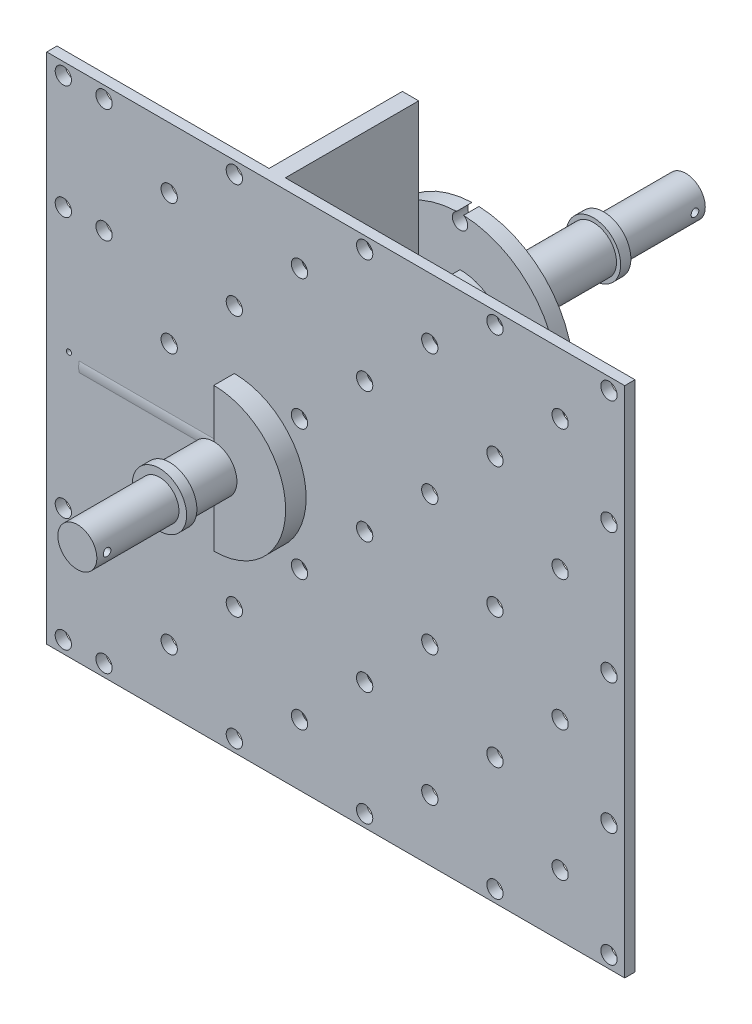
SolidWorks part; units mm, degrees
ref_plane "Front Plane" through (0, 0, 0) normal (0, 0, 1) x (1, 0, 0)
ref_plane "Top Plane" through (0, 0, 0) normal (0, 1, 0) x (1, 0, 0)
ref_plane "Right Plane" through (0, 0, 0) normal (1, 0, 0) x (0, 0, -1)
sketch "Sketch1" plane through (0, 0, 0) normal (0, 0, 1) x (1, 0, 0)
  circle A0 centre (0, 0) radius 3.8
extrude "Extrude1" add sketch "Sketch1" along normal blind 16
sketch "Sketch2" plane through (0, 0, 16) normal (0, 0, 1) x (1, 0, 0)
  circle A0 centre (0, 0) radius 4.5
extrude "Extrude2" add sketch "Sketch2" along normal blind 21
sketch "Sketch3" plane through (0, 0, 37) normal (0, 0, 1) x (1, 0, 0)
  circle A0 centre (0, 0) radius 11.1
extrude "Extrude3" add sketch "Sketch3" along normal blind 4
sketch "Sketch4" plane through (0, 0, 41) normal (0, 0, 1) x (1, 0, 0)
  circle A0 centre (0, 0) radius 6.35
  circle A1 centre (0, 0) radius 19.05
extrude "Extrude4" add sketch "Sketch4" along normal blind 3
sketch "Sketch5" plane through (0, 0, 44) normal (0, 0, 1) x (1, 0, 0)
  circle A1 centre (17.7, 0) radius 1.5
  circle A2 centre (0, -17.7) radius 1.5
  circle A3 centre (0, 17.7) radius 1.5
  circle A4 centre (-17.7, 0) radius 1.5
extrude "Extrude5" cut sketch "Sketch5" against normal up to surface (3 mm away) up to face at (19.05, 0, 41)
sketch "Sketch9" plane through (0, 0, 44) normal (0, 0, 1) x (1, 0, 0)
  line L0 (0, -20.6375) -> (0, 4.7625) construction
  line L1 (5.7625, -20.6375) -> (5.7625, 14.2875) construction
  line L2 (0, -6.35) -> (0, -9.525)
  line L3 (5.7625, -2.6676) -> (5.7625, -7.5841)
  line L4 (5.7625, 2.6676) -> (5.7625, 7.5841)
  line L5 (0, 6.35) -> (0, 9.525)
  circle A0 centre (0, 0) radius 9.525 construction
  arc A1 (0, -6.35) -> (5.7625, -2.6676) centre (0, 0) ccw
  arc A2 (0, -9.525) -> (5.7625, -7.5841) centre (0, 0) ccw
  arc A3 (5.7625, 2.6676) -> (0, 6.35) centre (0, 0) ccw
  circle A4 centre (0, 0) radius 6.35 construction
  arc A5 (5.7625, 7.5841) -> (0, 9.525) centre (0, 0) ccw
  dimension "D1" = 19.05
  dimension "D2" = 5.7625
extrude "Extrude9" add sketch "Sketch9" along normal blind 16
sketch "Sketch10" plane through (0, 0, 60) normal (0, 0, 1) x (1, 0, 0)
  line L0 (-76.2, 50) -> (52.3875, 50) construction
  line L1 (-76.2, -50) -> (52.3875, -50) construction
  line L2 (4.7625, -8.2489) -> (4.7625, -50)
  line L3 (4.7625, -50) -> (7.9422, -50)
  line L4 (0, -52.5) -> (34.925, -52.5) construction
  line L5 (14.2875, 52.5) -> (50.8, 52.5) construction
  line L6 (4.7625, -10) -> (4.7625, -62.5) construction
  line L7 (7.9375, -10) -> (7.9375, -60) construction
  line L8 (7.9422, -50) -> (7.9375, 50)
  line L9 (0, -6.35) -> (0, -9.525) construction
  line L11 (0, -6.35) -> (0, -9.525) construction
  line L12 (0, -9.525) -> (0, -6.35)
  line L13 (0, 6.35) -> (0, 9.525)
  line L14 (7.9375, 50) -> (4.7625, 50)
  line L15 (4.7625, 50) -> (4.7625, 8.2489)
  line L16 (101.6, 13) -> (-100.0125, 13) construction
  line L17 (4.7625, -4.2001) -> (4.7625, 4.2001)
  line L19 (4.7625, 9.05) -> (4.7625, -52.5) construction
  arc A0 (0, -6.35) -> (4.7625, -4.2001) centre (0, 0) ccw
  arc A2 (0, -9.525) -> (4.7625, -8.2489) centre (0, 0) ccw
  arc A3 (0, 6.35) -> (4.7625, 4.2001) centre (0, 0) cw
  arc A4 (5.7625, 2.6676) -> (0, 6.35) centre (0, 0) ccw construction
  arc A5 (0, 6.35) -> (0, -6.35) centre (0, 0) ccw construction
  arc A6 (0, 9.525) -> (4.7625, 8.2489) centre (0, 0) cw
extrude "Extrude10" add sketch "Sketch10" along normal blind 26
sketch "Sketch11" plane through (0, 0, 86) normal (0, 0, 1) x (1, 0, 0)
  line L0 (4.7625, -50) -> (7.9422, -50)
  line L1 (4.7625, 50) -> (7.9375, 50)
  line L2 (7.9422, -50) -> (76.1014, -50)
  line L3 (76.1014, -50) -> (76.1014, 50)
  line L4 (76.1014, 50) -> (7.9375, 50)
  line L5 (4.7625, 50) -> (-36.5715, 50)
  line L6 (-36.5715, 50) -> (-36.5715, -50)
  line L8 (-36.5715, -50) -> (4.7625, -50)
  line L9 (4.7625, -42.8625) -> (4.7625, 33.3375) construction
  line L10 (4.7625, -8.2489) -> (4.7625, -50) construction
  line L11 (4.7625, 50) -> (4.7625, 8.2489) construction
  circle A0 centre (50.8, 25.4) radius 1.5875
  circle A1 centre (25.4, 25.4) radius 1.5875
  circle A2 centre (0, 25.4) radius 1.5875
  circle A3 centre (-25.4, 25.4) radius 1.5875
  circle A4 centre (-32.2375, 1.5) radius 0.5
  circle A5 centre (0, 0) radius 1.5875
  circle A6 centre (25.4, 0) radius 1.5875
  circle A7 centre (50.8, 0) radius 1.5875
  circle A8 centre (50.8, -25.4) radius 1.5875
  circle A9 centre (25.4, -25.4) radius 1.5875
  circle A10 centre (0, -25.4) radius 1.5875
  circle A11 centre (-25.4, -25.4) radius 1.5875
  circle A12 centre (63.5, -38.1) radius 1.5875
  circle A13 centre (38.1, -38.1) radius 1.5875
  circle A14 centre (73.025, -47.625) radius 1.5875
  circle A15 centre (-12.7, -38.1) radius 1.5875
  circle A16 centre (12.7, -38.1) radius 1.5875
  circle A17 centre (-33.3375, -47.625) radius 1.5875
  circle A18 centre (63.5, -12.7) radius 1.5875
  circle A19 centre (38.1, -12.7) radius 1.5875
  circle A20 centre (12.7, -12.7) radius 1.5875
  circle A21 centre (63.5, 12.7) radius 1.5875
  circle A22 centre (38.1, 12.7) radius 1.5875
  circle A23 centre (63.5, 38.1) radius 1.5875
  circle A24 centre (38.1, 38.1) radius 1.5875
  circle A25 centre (12.7, 38.1) radius 1.5875
  circle A26 centre (-12.7, 38.1) radius 1.5875
  circle A27 centre (-12.7, 12.7) radius 1.5875
  circle A28 centre (73.025, 47.625) radius 1.5875
  circle A29 centre (50.8, -47.625) radius 1.5875
  circle A30 centre (25.4, -47.625) radius 1.5875
  circle A31 centre (0, -47.625) radius 1.5875
  circle A32 centre (-25.4, -47.625) radius 1.5875
  circle A33 centre (50.8, 47.625) radius 1.5875
  circle A34 centre (25.4, 47.625) radius 1.5875
  circle A35 centre (0, 47.625) radius 1.5875
  circle A36 centre (-25.4, 47.625) radius 1.5875
  circle A37 centre (-33.3375, 47.625) radius 1.5875
  circle A38 centre (73.025, 0) radius 1.5875
  circle A39 centre (73.025, -25.4) radius 1.5875
  circle A40 centre (73.025, 25.4) radius 1.5875
  circle A41 centre (-33.3375, 25.4) radius 1.5875
  circle A43 centre (-33.3375, -25.4) radius 1.5875
  circle A44 centre (-12.7, -12.7) radius 1.5875
  circle A45 centre (12.7, 12.7) radius 1.5875
  point P117 (-32.2375, 1.5)
  dimension "D1" = 37
  dimension "D2" = 1.5
extrude "Extrude11" add sketch "Sketch11" along normal blind 2
sketch "Sketch16" plane through (0, 0, 88) normal (0, 0, 1) x (1, 0, 0)
  line L0 (0, -14) -> (0, 14)
  circle A0 centre (0, 0) radius 14 construction
  arc A1 (0, -14) -> (0, 14) centre (0, 0) ccw
extrude "Extrude15" add sketch "Sketch16" along normal blind 4 separate body
sketch "Sketch17" plane through (0, 0, 92) normal (0, 0, 1) x (1, 0, 0)
  circle A0 centre (0, 0) radius 4.5
extrude "Extrude16" add sketch "Sketch17" along normal blind 10.6
sketch "Sketch18" plane through (0, 0, 102.6) normal (0, 0, 1) x (1, 0, 0)
  circle A0 centre (0, 0) radius 3.8
extrude "Extrude17" add sketch "Sketch18" along normal blind 16
sketch "Sketch19" plane through (0, 0, 16) normal (0, 0, -1) x (-1, 0, 0)
  circle A0 centre (0, 0) radius 5.3
extrude "Extrude19" add sketch "Sketch19" against normal blind 2
sketch "Sketch20" plane through (0, 0, 102.6) normal (0, 0, 1) x (1, 0, 0)
  circle A0 centre (0, 0) radius 5.3
extrude "Extrude20" add sketch "Sketch20" against normal blind 2
sketch "Sketch21" plane through (4.7625, 0, 0) normal (-1, 0, 0) x (0, 0, 1)
  line L0 (86, 50) -> (86, -50) construction
  circle A0 centre (83.8, 0) radius 2.2
  circle A1 centre (83.8, 0) radius 4.3125
  point P0 (83.8, 0)
  point P1 (86, 0)
  dimension "D1" = 2.2
extrude "Extrude21" add sketch "Sketch21" along normal blind 35
sketch "Sketch22" plane through (4.7625, 0, 0) normal (-1, 0, 0) x (0, 0, 1)
  line L0 (86, 50) -> (86, -50) construction
  circle A0 centre (83.8, 0) radius 1.5
  point P0 (83.8, 0)
  dimension "D1" = 2.2
extrude "Extrude22" cut sketch "Sketch22" against normal blind 25
sketch "Sketch23" plane through (0, 0, 0) normal (1, 0, 0) x (0, 0, -1)
  line L0 (-118.6, 3.8) -> (-118.6, -3.8) construction
  circle A0 centre (-116.6, 0) radius 0.75
  circle A1 centre (-2, 0) radius 0.75
  point P0 (-116.6, 0)
  point P5 (-2, 0)
  dimension "D2" = 2
  dimension "D1" = 2
extrude "Extrude23" cut sketch "Sketch23" against normal through all and the other way through all
